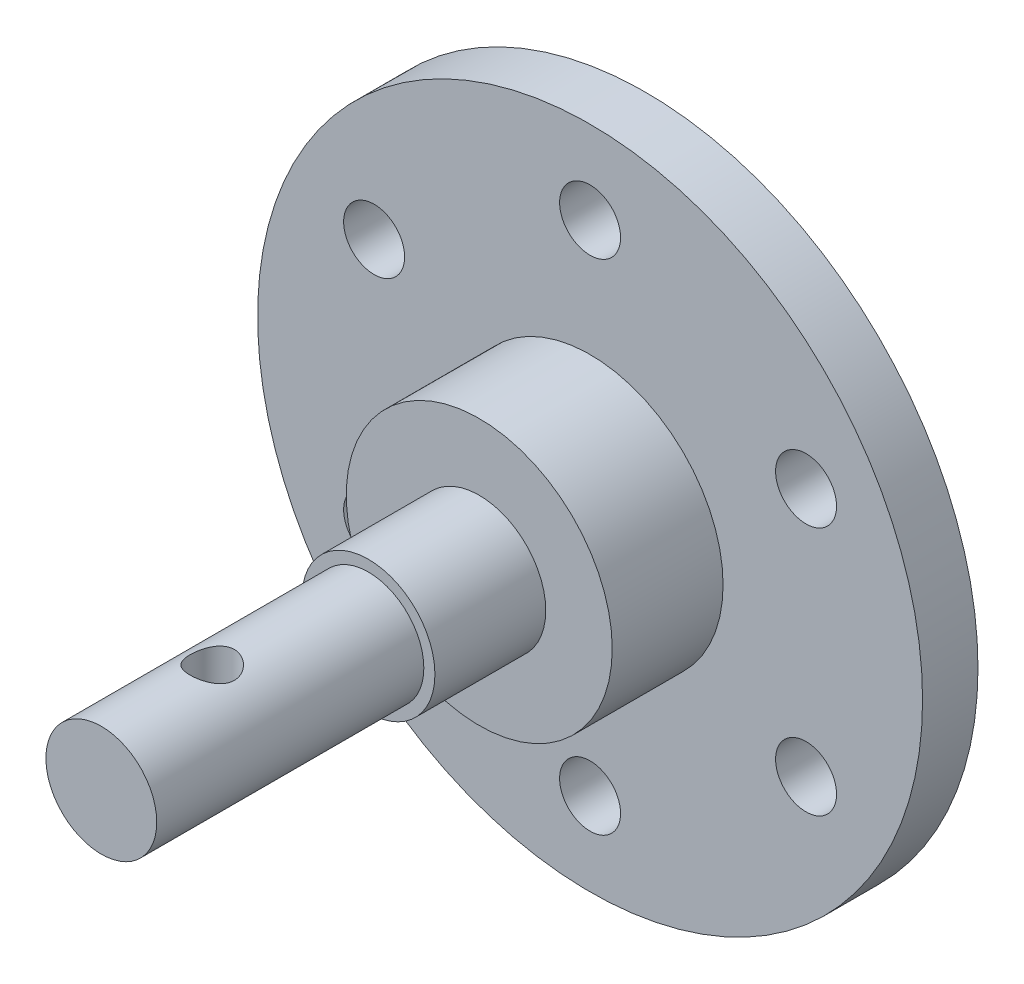
SolidWorks part; units mm, degrees
ref_plane "前视基准面" through (0, 0, 0) normal (0, 0, 1) x (1, 0, 0)
ref_plane "上视基准面" through (0, 0, 0) normal (0, 1, 0) x (1, 0, 0)
ref_plane "右视基准面" through (0, 0, 0) normal (1, 0, 0) x (0, 0, -1)
sketch "草图1" plane through (0, 0, 0) normal (0, 0, 1) x (1, 0, 0)
  line L0 (0, 0) -> (0, 13.9022) construction
  line L1 (0, 0) -> (0, 55.2697) construction
  circle A0 centre (0, 0) radius 30
  circle A1 centre (0, 0) radius 22.5 construction
  circle A2 centre (0, 22.5) radius 2.75
  circle A3 centre (19.4856, 11.25) radius 2.75
  circle A4 centre (19.4856, -11.25) radius 2.75
  circle A5 centre (0, -22.5) radius 2.75
  circle A6 centre (-19.4856, -11.25) radius 2.75
  circle A7 centre (-19.4856, 11.25) radius 2.75
  point P20 (0, 0)
  dimension "D1" = 6
extrude "凸台-拉伸1" add sketch "草图1" along normal blind 5
sketch "草图2" plane through (0, 0, 5) normal (0, 0, 1) x (1, 0, 0)
  circle A0 centre (0, 0) radius 12
extrude "凸台-拉伸2" add sketch "草图2" along normal blind 10
sketch "草图3" plane through (0, 0, 15) normal (0, 0, 1) x (1, 0, 0)
  circle A0 centre (0, 0) radius 6
extrude "凸台-拉伸3" add sketch "草图3" along normal blind 10
sketch "草图5" plane through (0, 0, 25) normal (0, 0, 1) x (1, 0, 0)
  circle A0 centre (0, 0) radius 5
extrude "凸台-拉伸4" add sketch "草图5" along normal blind 24.1
sketch "草图6" plane through (0, 0, 0) normal (0, 1, 0) x (1, 0, 0)
  line L0 (0, -49.1) -> (0, -39.1) construction
  line L1 (-5, -49.1) -> (5, -49.1) construction
  circle A0 centre (0, -39.1) radius 2
  dimension "D1" = 10
extrude "切除-拉伸1" cut sketch "草图6" against normal blind 10 and the other way blind 10
